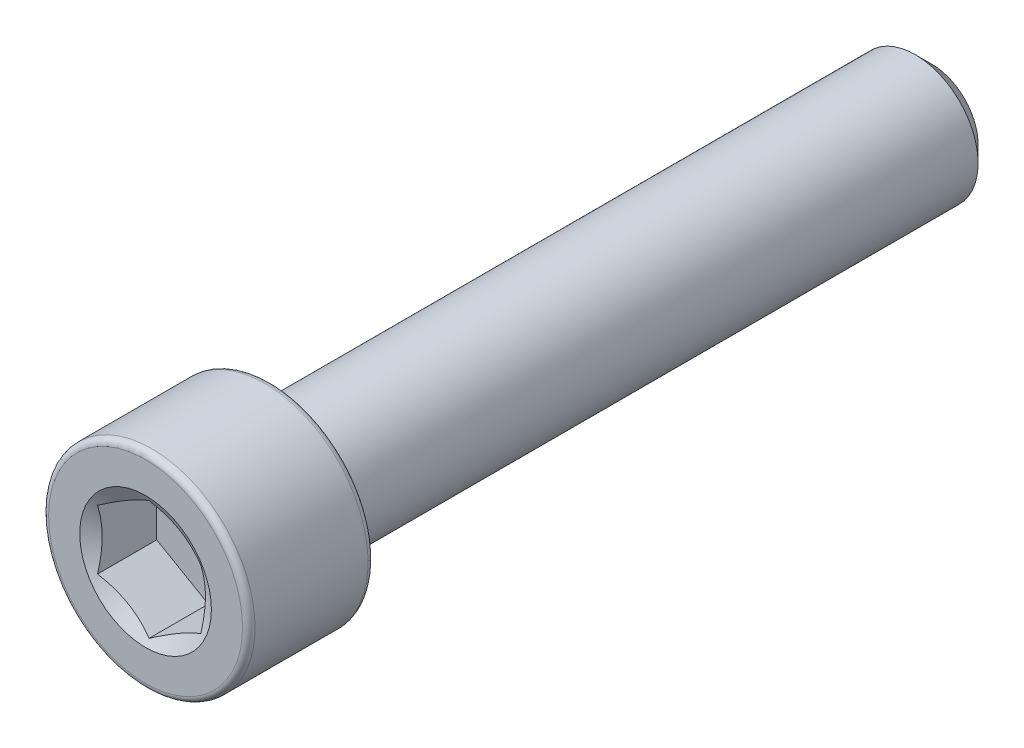
SolidWorks part; units mm, degrees
ref_plane "Front Plane" through (0, 0, 0) normal (0, 0, 1) x (1, 0, 0)
ref_plane "Top Plane" through (0, 0, 0) normal (0, 1, 0) x (1, 0, 0)
ref_plane "Right Plane" through (0, 0, 0) normal (1, 0, 0) x (0, 0, -1)
sketch "Sketch1" plane through (0, 0, 0) normal (1, 0, 0) x (0, 0, -1)
  line L0 (15.113, 0) -> (-15.113, 0) construction
  line L1 (-10.287, 3.9687) -> (-10.287, -3.9688) construction
  line L2 (15.113, 2.413) -> (15.113, -2.413) construction
  line L3 (15.0469, 2.5276) -> (15.576, 1.611) construction
  line L4 (15.5099, 1.7256) -> (15.6422, 1.7256) construction
  line L5 (15.576, 1.611) -> (16.1052, 2.5276) construction
  line L6 (16.1052, 2.5276) -> (15.0469, 2.5276) construction
  line L7 (15.576, 1.7256) -> (15.576, 1.611) construction
  line L8 (15.576, 2.5276) -> (15.576, 2.413) construction
  line L9 (16.039, 2.413) -> (15.113, 2.413) construction
  point P4 (-10.287, 0)
  point P6 (-10.287, 1.9844)
  point P7 (12.4672, -2.413)
  point P20 (15.576, 2.4703)
  dimension "Head Height" = 4.826
  dimension "Head Diameter" = 7.9375
  dimension "Drive Size" = 3.9688
  dimension "Length" = 25.4
  dimension "Screw Size Decimal Equivalent" = 4.826
  dimension "Pitch" = 1.0583
  dimension "Pitch/8" = 0.1323
  dimension "Thread Note" = 2.6458
sketch "Sketch2" plane through (0, 0, 0) normal (1, 0, 0) x (0, 0, -1)
  line L0 (15.113, 0) -> (15.113, 1.778)
  line L1 (15.113, 2.413) -> (15.113, -2.413) construction
  line L2 (15.113, 1.778) -> (14.478, 2.413)
  line L3 (14.478, 2.413) -> (-10.287, 2.413)
  line L4 (-10.287, 2.413) -> (-10.287, 3.7274)
  line L5 (-10.5283, 3.9687) -> (-14.8717, 3.9687)
  line L6 (-15.113, 3.7274) -> (-15.113, 0)
  line L7 (15.113, 0) -> (-15.113, 0) construction
  line L8 (-15.113, 0) -> (15.113, 0)
  arc A0 (-10.287, 3.7274) -> (-10.5283, 3.9687) centre (-10.5283, 3.7274) ccw
  arc A1 (-14.8717, 3.9687) -> (-15.113, 3.7274) centre (-14.8717, 3.7274) ccw
  point P19 (-10.287, 3.9687)
  dimension "D3" = 0.2413
  dimension "D1" = 0.635
  dimension "D2" = 45
revolve "Revolve1" add sketch "Sketch2" angle 360 about L0
sketch "Sketch3" plane through (0, 0, 0) normal (0, 0, 1) x (1, 0, 0)
  line L1 (-1.9844, 1.1457) -> (-1.9844, -1.1457)
  line L2 (-1.9844, -1.1457) -> (0, -2.2914)
  line L3 (0, -2.2914) -> (1.9844, -1.1457)
  line L4 (1.9844, -1.1457) -> (1.9844, 1.1457)
  line L5 (1.9844, 1.1457) -> (0, 2.2914)
  line L6 (0, 2.2914) -> (-1.9844, 1.1457)
  circle A0 centre (0, 0) radius 1.9844 construction
  circle A1 centre (0, 0) radius 3.9687 construction
extrude "Cut-Extrude1" cut sketch "Sketch3" against normal blind 2.413 from vertex starting at point (0, 0, 15.113)
sketch "Sketch4" plane through (0, 0, 15.113) normal (0, 0, 1) x (1, 0, 0)
  line L0 (0, 2.2914) -> (0, 2.7701) construction
  line L1 (0, 2.7701) -> (0, 3.2488) construction
  line L2 (0, 3.2488) -> (0, 3.7274) construction
  circle A0 centre (0, 0) radius 2.5307
  point P12 (0, 2.5307)
extrude "Cut-Extrude2" cut sketch "Sketch4" against normal through all draft 60
split "Split1" [suppressed] bodies to split 106 112
sketch "Sketch5" [suppressed] plane through (0, 0, 0) normal (1, 0, 0) x (0, 0, -1)
  line L0 (15.5099, 1.7256) -> (15.6422, 1.7256)
  line L1 (15.6422, 1.7256) -> (16.0721, 2.4703)
  line L2 (16.0721, 2.4703) -> (15.0799, 2.4703)
  line L3 (15.0799, 2.4703) -> (15.5099, 1.7256)
  line L4 (15.0469, 2.5276) -> (15.576, 1.611) construction
sketch "Sketch6" [suppressed] plane through (0, 0, -15.113) normal (0, 0, -1) x (-1, 0, 0)
  circle A0 centre (0, 0) radius 2.413
curve "Helix/Spiral1" [suppressed] pitch 1.0583 height 26.4583 turns 25
sweep "Cut-Sweep1" [suppressed] cut profiles "Sketch5" path "Helix/Spiral1"
sketch "Sketch7" [suppressed] plane through (0, 0, 10.287) normal (0, 0, -1) x (-1, 0, 0)
  circle A0 centre (0, 0) radius 2.4638
  circle A1 centre (0, 0) radius 2.413 construction
  dimension "D1" = 0.0508
extrude "Boss-Extrude1" [suppressed] add sketch "Sketch7" along normal blind 3.175 draft 20 and the other way blind 0.4826
ref_plane "Plane1" [suppressed] through (0, 0, 11.8796) normal (0, 0, -1) x (-1, 0, 0)
sketch "Sketch13" [suppressed] plane through (0, 0, 11.8796) normal (0, 0, -1) x (-1, 0, 0)
  line L0 (0.0992, 3.9675) -> (0, 0) construction
  line L1 (0, 0) -> (-0.0992, 3.9675) construction
  line L3 (0.0976, 3.902) -> (0.0992, 3.9675)
  line L6 (-0.0976, 3.902) -> (-0.0992, 3.9675)
  arc A1 (0.0992, 3.9675) -> (-0.0992, 3.9675) centre (0, 0) ccw
  circle A2 centre (0, 0) radius 3.9687 construction
  arc A3 (0.0976, 3.902) -> (-0.0976, 3.902) centre (0, 0) ccw
  point P2 (0, 3.9687)
  dimension "D3" = 0.0655
  dimension "D1" = 0.1984
extrude "Cut-Extrude3" [suppressed] cut sketch "Sketch13" against normal blind 2.6929
chamfer "Chamfer3" [suppressed] distance 0.0655 angle 60
chamfer "Chamfer4" [suppressed] distance 0.0655 angle 85
pattern_circular "CirPattern2" [suppressed] count 50 over 360 about axis through (0, 0, -15.113) along (0, 0, 1) of bodies 134
equation "\"Pitch/8@Sketch1\" = \"Pitch@Sketch1\" / 8"
equation "\"Thread Note@Sketch1\"=\"Pitch@Sketch1\" * 2.5"
equation "\"D1@Sketch2\"=\"Pitch@Sketch1\"*.60"
equation "\"D3@Sketch2\"=\"Head Height@Sketch1\"*.05"
equation "\"D1@Cut-Extrude1\" = \"Head Height@Sketch1\" * .5"
equation "\"D3@Helix/Spiral1\" = \"Length@Sketch1\" + \"Pitch@Sketch1\""
equation "\"D4@Helix/Spiral1\" = \"Pitch@Sketch1\""
equation "\"D2@Boss-Extrude1\" = \"Head Height@Sketch1\" * .1"
equation "\"D1\"= \"Screw Size Decimal Equivalent@Sketch1\" * .4"
equation "\"D1@Plane1\"=\"Head Height@Sketch1\" * .33"
equation "\"D1@Cut-Extrude3\"=( \"Head Height@Sketch1\" - \"D1@Plane1\" - \"D3@Sketch2\" )  * .9"
equation "\"D1@Chamfer3\"=\"D3@Sketch13\""
equation "\"D1@Chamfer4\"=\"D3@Sketch13\""
equation "\"D1@CirPattern2\"=( \"Head Diameter@Sketch1\" * pi )  /  ( 2.5*\"D1@Sketch13\" )"
equation "\"D1@Sketch13\"=\"Head Diameter@Sketch1\" * .025"
equation "\"D3@Sketch13\"=\"D1@Sketch13\"*.33"
equation "\"D1@Boss-Extrude1\"=\"Pitch@Sketch1\"*3"
